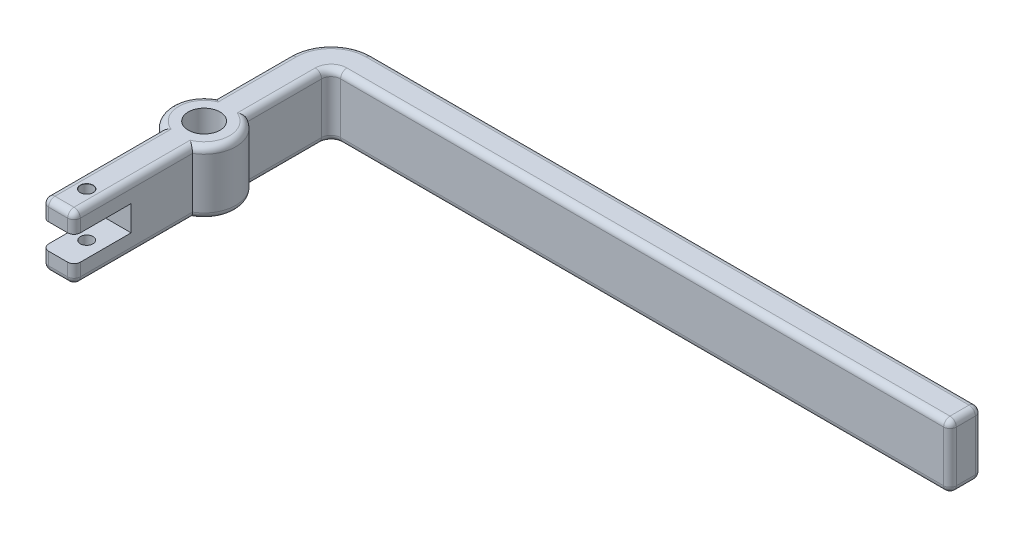
SolidWorks part; units mm, degrees
material "1060 Alloy"
ref_plane "Front Plane" through (0, 0, 0) normal (0, 0, 1) x (1, 0, 0)
ref_plane "Top Plane" through (0, 0, 0) normal (0, 1, 0) x (1, 0, 0)
ref_plane "Right Plane" through (0, 0, 0) normal (1, 0, 0) x (0, 0, -1)
sketch "Sketch1" plane through (0, 0, 0) normal (0, 1, 0) x (1, 0, 0)
  line L0 (0, 0) -> (0, 16) construction
  line L9 (4, 20) -> (100, 20) construction
  line L10 (0, 0) -> (0, -21) construction
  line L11 (2.5, -4.3301) -> (2.5, -21)
  line L12 (2.5, 4.3301) -> (2.5, 16)
  line L13 (4, 17.5) -> (100, 17.5)
  line L14 (-2.5, -4.3301) -> (-2.5, -21)
  line L15 (-2.5, 4.3301) -> (-2.5, 16)
  line L16 (4, 22.5) -> (100, 22.5)
  line L17 (-2.5, 0) -> (-2.5, -21) construction
  line L18 (2.5, 0) -> (2.5, -21) construction
  line L19 (-2.5, 0) -> (-2.5, 16) construction
  line L20 (2.5, 0) -> (2.5, 16) construction
  line L21 (-2.5, -21) -> (2.5, -21)
  line L22 (100, 22.5) -> (100, 17.5)
  circle A5 centre (0, 0) radius 2.5
  arc A6 (2.5, -4.3301) -> (2.5, 4.3301) centre (0, 0) ccw
  arc A7 (0, 16) -> (4, 20) centre (4, 16) cw construction
  arc A8 (2.5, 16) -> (4, 17.5) centre (4, 16) cw
  arc A9 (-2.5, 16) -> (4, 22.5) centre (4, 16) cw
  arc A10 (-2.5, 4.3301) -> (-2.5, -4.3301) centre (0, 0) ccw
  point P25 (0, -18.5)
  dimension "D1" = 5
  dimension "D6" = 2.5
  dimension "D7" = 2.5
  dimension "D8" = 100
  dimension "D2" = 10
  dimension "D3" = 4
  dimension "D4" = 20
  dimension "D5" = 18.5
  dimension "D9" = 2.5
extrude "Boss-Extrude1" add sketch "Sketch1" along normal blind 10
sketch "Sketch2" plane through (0, 0, 21) normal (0, 0, 1) x (1, 0, 0)
  line L0 (-2.5, 7) -> (2.5, 7)
  line L1 (-2.5, 10) -> (-2.5, 0) construction
  line L2 (2.5, 10) -> (2.5, 0) construction
  line L3 (2.5, 7) -> (2.5, 3)
  line L4 (2.5, 10) -> (2.5, 0) construction
  line L5 (2.5, 3) -> (-2.5, 3)
  line L6 (-2.5, 10) -> (-2.5, 0) construction
  line L7 (-2.5, 3) -> (-2.5, 7)
  line L8 (-2.5, 10) -> (2.5, 10) construction
  dimension "D1" = 3
  dimension "D2" = 3
extrude "Cut-Extrude1" cut sketch "Sketch2" against normal blind 7
sketch "Sketch3" plane through (0, 10, 0) normal (0, 1, 0) x (1, 0, 0)
  point P0 (0, -18.5)
hole_wizard "Ø2.0mm Dowel Hole1" positions "Sketch3" profile "Sketch4" hole size "Ø2.0" standard "ANSI Metric" end condition through all
sketch "Sketch4" plane through (0, 10, 18.5) normal (1, 0, 0) x (0, 0, 1)
  line L0 (0, 0) -> (0, 10)
  line L1 (0, 10) -> (1, 10)
  line L2 (1, 10) -> (1, 0.025)
  line L3 (1, 0.025) -> (1.025, 0)
  line L5 (1.025, 0) -> (0, 0)
  line L6 (-1, 0.025) -> (-1.025, 0) construction
  line L11 (0, -6.35) -> (0, 107.95) construction
  dimension "Thru Hole Dia." = 2
  dimension "Thru Hole Depth" = 10
  dimension "Near C'Sink Dia." = 2.05
  dimension "Near C'Sink Angle" = 90
sketch "Sketch5" plane through (0, 0, 21) normal (0, 0, 1) x (1, 0, 0)
  line L0 (-2.5, 10) -> (2.5, 10)
  line L1 (2.5, 10) -> (2.5, 7)
  line L2 (2.5, 7) -> (-2.5, 7)
  line L3 (-2.5, 7) -> (-2.5, 10)
  line L4 (-2.5, 3) -> (2.5, 3)
  line L5 (2.5, 3) -> (2.5, 0)
  line L6 (2.5, 0) -> (-2.5, 0)
  line L7 (-2.5, 0) -> (-2.5, 3)
extrude "Boss-Extrude2" add sketch "Sketch5" along normal blind 2
fillet "Fillet1" radius 1 16 edges at (2.5, 10, -10.1651) (2.9393, 10, -17.0607) (2.5, 0, -10.1651) (2.9393, 0, -17.0607) (-2.5, 10, -10.1651) (-0.5962, 10, -20.5962) (-2.5, 0, -10.1651) (-0.5962, 0, -20.5962) (100, 10, -20) (100, 0, -20) (52, 10, -17.5) (100, 5, -17.5) (52, 0, -17.5) (100, 5, -22.5) (52, 10, -22.5) (52, 0, -22.5)
fillet "Fillet2" radius 1 14 edges at (2.5, 10, 13.6651) (-2.5, 10, 13.6651) (-4.9701, 0, -0.5462) (4.9701, 0, -0.5462) (-2.5, 0, 13.6651) (2.5, 0, 13.6651) (4.9701, 10, -0.5462) (-4.9701, 10, -0.5462) (0, 10, 23) (2.5, 8.5, 23) (-2.5, 8.5, 23) (2.5, 1.5, 23) (-2.5, 1.5, 23) (0, 0, 23)
sketch "Sketch6" plane through (-2.5, 0, 0) normal (-1, 0, 0) x (0, 0, 1)
  line L0 (10, 5) -> (10, 10) construction
  line L1 (3.7081, 10) -> (22, 10) construction
  line L2 (10, 5) -> (10, 0) construction
  line L3 (22, 0) -> (3.7081, 0) construction
  circle A0 centre (10, 5) radius 2
  dimension "D3" = 4
  dimension "D1" = 5
  dimension "D2" = 8.5
extrude "Boss-Extrude3" add sketch "Sketch6" along normal blind 1.5
chamfer "Chamfer1" distance 0.5 angle 45 1 edges at (-4, 5, 12)
